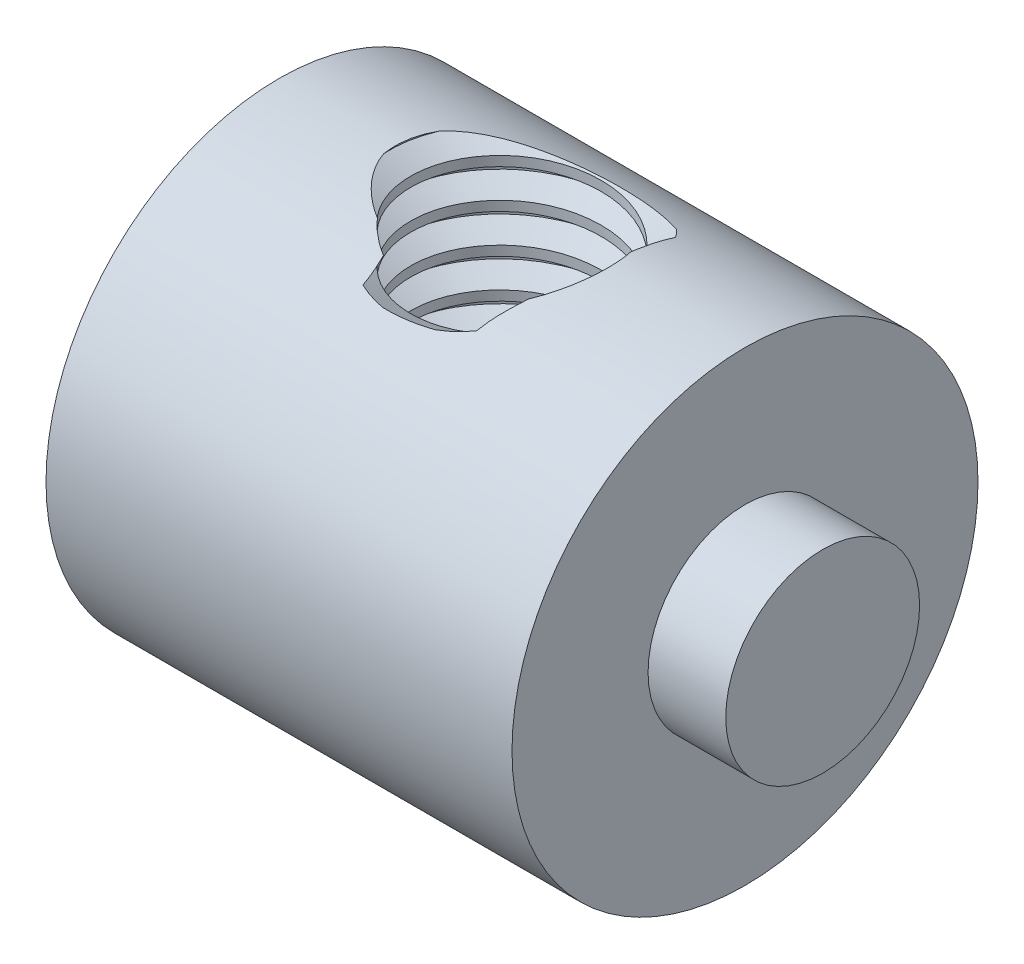
SolidWorks part; units mm, degrees
ref_plane "Front Plane" through (0, 0, 0) normal (0, 0, 1) x (1, 0, 0)
ref_plane "Top Plane" through (0, 0, 0) normal (0, 1, 0) x (1, 0, 0)
ref_plane "Right Plane" through (0, 0, 0) normal (1, 0, 0) x (0, 0, -1)
sketch "Sketch1" plane through (0, 0, 0) normal (0, 0, 1) x (1, 0, 0)
  line L0 (0, 0) -> (25.4, 0)
  line L1 (25.4, 0) -> (25.4, 3.9624)
  line L2 (25.4, 3.9624) -> (22.225, 3.9624)
  line L3 (22.225, 3.9624) -> (22.225, 9.525)
  line L4 (22.225, 9.525) -> (3.175, 9.525)
  line L5 (3.175, 9.525) -> (3.175, 3.9624)
  line L6 (3.175, 3.9624) -> (0, 3.9624)
  line L7 (0, 3.9624) -> (0, 0)
  dimension "D1" = 25.4
  dimension "D2" = 9.525
  dimension "D3" = 3.9624
  dimension "D4" = 19.05
revolve "Revolve1" add sketch "Sketch1" angle 360 about L0
sketch "Sketch2" plane through (0, 0, 0) normal (0, 1, 0) x (1, 0, 0)
  line L0 (3.175, 9.525) -> (3.175, -9.525) construction
  circle A0 centre (12.7, 0) radius 4.7625
  dimension "D1" = 9.525
  dimension "D2" = 9.525
extrude "Cut-Extrude1" cut sketch "Sketch2" against normal through all both and the other way through all
sketch "Sketch3" plane through (0, 0, 0) normal (0, 1, 0) x (1, 0, 0)
  circle A0 centre (12.7, 0) radius 4.7625 construction
  circle A1 centre (12.7, 0) radius 4.7625
  circle A2 centre (12.7, 0) radius 7.6998
extrude "Boss-Extrude1" add sketch "Sketch3" along normal mid plane 20.32
thread "Thread1" pitch 1.5875 start angle 0, offset 1.5875, length 0, pitch 1.5875, diameter 9.525
ref_plane "Plane1" through (17.4625, -11.7475, 0) normal (0, 0, 1) x (1, 0, 0)
sketch "Thread Profile1" plane through (17.4625, -11.7475, 0) normal (0, 0, 1) x (1, 0, 0)
  line L0 (0, 0) -> (0, 1.5875) construction
  line L11 (0, 0) -> (0, 1.3891)
  line L12 (0, 1.3891) -> (-0.8593, 0.893)
  line L13 (-0.8593, 0.893) -> (-0.8593, 0.4961)
  line L15 (-0.8593, 0.4961) -> (0, 0)
  line L17 (-0.8593, 0.6945) -> (0, 0.6945) construction
  point P2 (0, 0)
  dimension "Pitch" = 1.5875
  dimension "Profile_Angle" = 60
  dimension "Profile_Land" = 0.3969
  dimension "Profile_Height" = 0.8593
sketch "Sketch9" plane through (0, 0, 0) normal (0, 0, 1) x (1, 0, 0)
  line L1 (22.225, 9.525) -> (3.2684, 9.525)
  line L2 (22.225, 9.525) -> (22.225, 12.9503)
  line L3 (22.225, 12.9503) -> (3.2684, 12.9503)
  line L4 (3.2684, 9.525) -> (3.2684, 12.9503)
revolve "Cut-Revolve1" cut sketch "Sketch9" angle 360 about axis through (0, 0, 0) along (-1, 0, 0)
